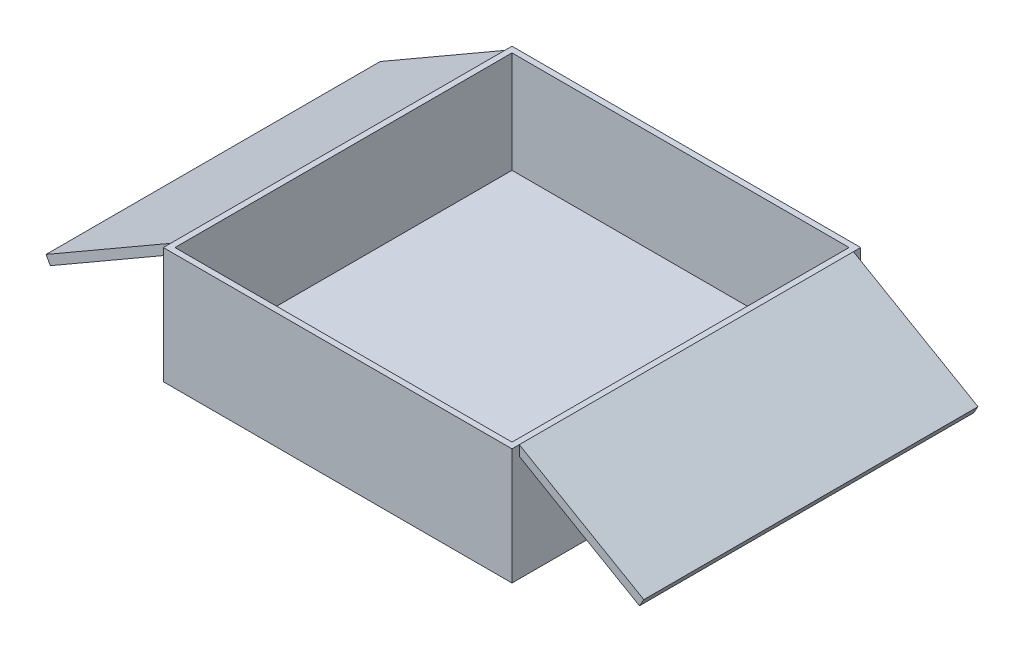
SolidWorks part; units mm, degrees
ref_plane "Front Plane" through (0, 0, 0) normal (0, 0, 1) x (1, 0, 0)
ref_plane "Top Plane" through (0, 0, 0) normal (0, 1, 0) x (1, 0, 0)
ref_plane "Right Plane" through (0, 0, 0) normal (1, 0, 0) x (0, 0, -1)
sketch "Sketch1" plane through (0, 0, 0) normal (0, 1, 0) x (1, 0, 0)
  line L0 (-58, 58) -> (58, 58)
  line L1 (-60, 60) -> (60, 60)
  line L2 (-60, 60) -> (-60, -60)
  line L3 (-60, -60) -> (60, -60)
  line L4 (60, 60) -> (60, -60)
  line L5 (-60, 60) -> (60, -60) construction
  line L6 (-60, -60) -> (60, 60) construction
  line L7 (58, 58) -> (58, -58)
  line L8 (-58, -58) -> (58, -58)
  line L9 (-58, 58) -> (-58, -58)
  point P0 (0, 0)
  dimension "D1" = 120
  dimension "D2" = 2
extrude "Boss-Extrude1" add sketch "Sketch1" along normal blind 5 contours L4 L1 L2 L3 L9 L0 L7 L8 | L0 L7 L8 L9 region at (0, 0, -58.3029)
extrude "Boss-Extrude2" add sketch "Sketch1<3>" along normal blind 40
sketch "Sketch1<3>" plane through (0, 0, 0) normal (0, 1, 0) x (1, 0, 0) same geometry as "Sketch1"
sketch "Sketch2" plane through (0, 0, 0) normal (0, 0, 1) x (1, 0, 0)
  line L0 (60, 40) -> (102.8683, 15.25)
  line L1 (102.8683, 15.25) -> (101.3683, 12.6519)
  line L2 (101.3683, 12.6519) -> (60, 36.5359)
  line L3 (60, 40) -> (60, 0) construction
  line L4 (60, 36.5359) -> (60, 40)
  dimension "D1" = 60
  dimension "D2" = 49.5
  dimension "D3" = 3
extrude "Boss-Extrude3" add sketch "Sketch2" along normal mid plane 115
mirror "Mirror1" about plane through (0, 0, 0) normal (1, 0, 0) of "Boss-Extrude3"
ref_plane "Plane1" through (0, 40, 0) normal (0, 1, 0) x (1, 0, 0)
sketch "Sketch3" plane through (0, 40, 0) normal (0, 1, 0) x (1, 0, 0)
  point P0 (0, 0)
